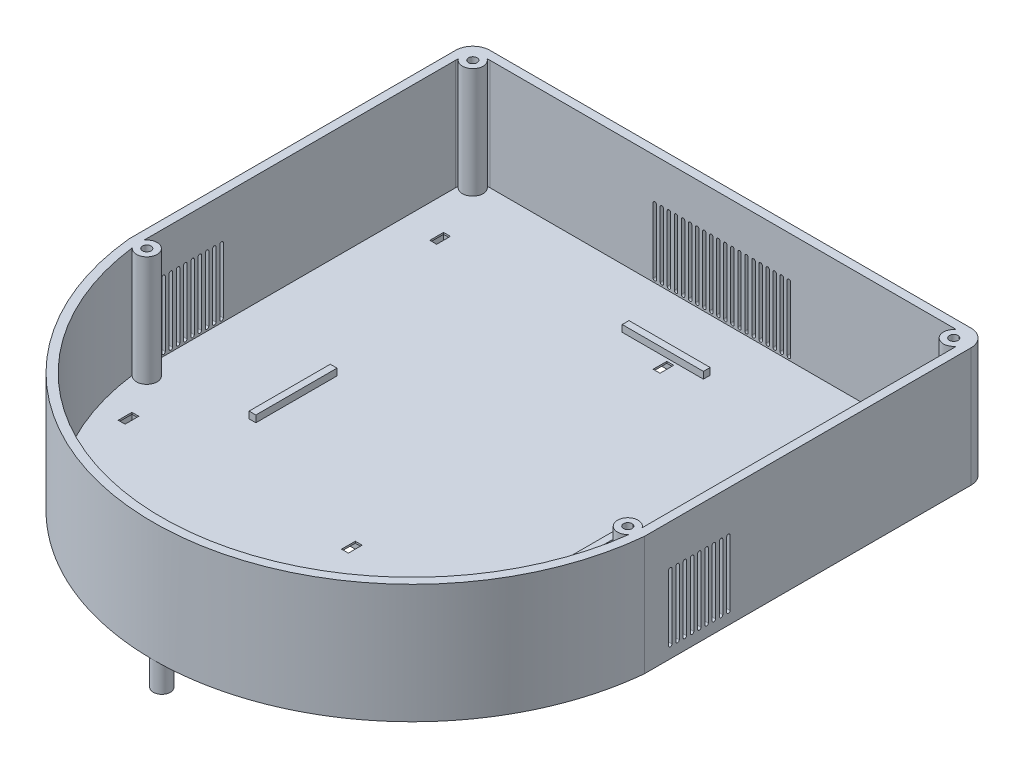
SolidWorks part; units mm, degrees
material "6063-O"
ref_plane "Front Plane" through (0, 0, 0) normal (0, 0, 1) x (1, 0, 0)
ref_plane "Top Plane" through (0, 0, 0) normal (0, 1, 0) x (1, 0, 0)
ref_plane "Right Plane" through (0, 0, 0) normal (1, 0, 0) x (0, 0, -1)
sketch "Sketch1" plane through (0, 0, 0) normal (0, 1, 0) x (1, 0, 0)
  line L1 (-190.5, -213.36) -> (190.5, -213.36)
  line L2 (-190.5, -213.36) -> (-190.5, 213.36)
  line L3 (-190.5, 213.36) -> (190.5, 213.36)
  line L4 (190.5, -213.36) -> (190.5, 213.36)
  line L5 (-190.5, -213.36) -> (190.5, 213.36) construction
  line L6 (-190.5, 213.36) -> (190.5, -213.36) construction
  arc A0 (190.5, -40.64) -> (-190.5, -40.64) centre (0, -21.9449) cw
  point P0 (0, 0)
  dimension "D1" = 381
  dimension "D2" = 426.72
  dimension "D3" = 254
extrude "Boss-Extrude1" add sketch "Sketch1" along normal blind 88 contours L4 L3 L2 L1 region at (0, 0, -17.9529)
shell "Shell1" thickness 6.35 removed face at (0, 88, -43.18)
fillet "Fillet2" radius 12.7 4 edges at (-190.5, 44, -213.36) (190.5, 44, -213.36) (184.15, 47.175, -207.01) (-184.15, 47.175, -207.01)
sketch "Sketch3" plane through (0, 6.35, 0) normal (0, 1, 0) x (1, 0, 0)
  line L0 (-177.8, 200.66) -> (-177.8, -40.3265) construction
  circle A2 centre (-177.8, 200.66) radius 7.62
  arc A5 (-177.8, 213.36) -> (-190.5, 200.66) centre (-177.8, 200.66) ccw construction
  circle A6 centre (-177.8, -40.3265) radius 7.62
  circle A8 centre (-177.8, 200.66) radius 3.175
  circle A9 centre (-177.8, -40.3265) radius 3.175
  dimension "D1" = 15.24
  dimension "D2" = 6.35
extrude "Boss-Extrude2" add sketch "Sketch3" along normal up to surface (81.65 mm away) up to face at (0, 88, -96.5501)
mirror "Mirror1" about plane through (0, 0, 0) normal (1, 0, 0) of "Boss-Extrude2"
sketch "Sketch4" plane through (0, 0, 0) normal (0, -1, 0) x (1, 0, 0)
  line L0 (-177.8, -213.36) -> (177.8, -213.36) construction
  line L1 (-161.29, -162.56) -> (161.29, -162.56)
  line L2 (-161.29, -162.56) -> (-161.29, -149.86)
  line L3 (-161.29, -149.86) -> (161.29, -149.86)
  line L4 (161.29, -162.56) -> (161.29, -149.86)
  line L5 (-161.29, 67.818) -> (161.29, 67.818)
  line L6 (-161.29, 67.818) -> (-161.29, 80.518)
  line L7 (-161.29, 80.518) -> (161.29, 80.518)
  line L8 (161.29, 67.818) -> (161.29, 80.518)
  point P8 (0, 80.518)
  dimension "D1" = 322.58
  dimension "D2" = 12.7
  dimension "D3" = 217.678
  dimension "D4" = 50.8
extrude "Cut-Extrude2" cut sketch "Sketch4" against normal blind 5.08
sketch "Sketch5" plane through (0, 5.08, 0) normal (0, -1, 0) x (1, 0, 0)
  line L1 (-160.02, 79.248) -> (-154.94, 79.248)
  line L2 (-160.02, 79.248) -> (-160.02, 69.088)
  line L3 (-160.02, 69.088) -> (-154.94, 69.088)
  line L4 (-154.94, 79.248) -> (-154.94, 69.088)
  line L5 (5.08, 79.248) -> (10.16, 79.248)
  line L6 (5.08, 79.248) -> (5.08, 69.088)
  line L7 (5.08, 69.088) -> (10.16, 69.088)
  line L8 (10.16, 79.248) -> (10.16, 69.088)
  line L9 (-161.29, 80.518) -> (-161.29, 67.818) construction
  line L10 (-161.29, 80.518) -> (-161.29, 67.818) construction
  line L11 (-161.29, -149.86) -> (-161.29, -162.56) construction
  line L12 (-160.02, -151.13) -> (-154.94, -151.13)
  line L13 (-160.02, -151.13) -> (-160.02, -161.29)
  line L14 (-160.02, -161.29) -> (-154.94, -161.29)
  line L15 (-154.94, -151.13) -> (-154.94, -161.29)
  line L16 (5.08, -151.13) -> (10.16, -151.13)
  line L17 (5.08, -151.13) -> (5.08, -161.29)
  line L18 (5.08, -161.29) -> (10.16, -161.29)
  line L19 (10.16, -151.13) -> (10.16, -161.29)
  point P12 (-161.29, 74.168)
  point P13 (-160.02, 74.168)
  point P14 (5.08, 74.168)
  point P25 (-161.29, -156.21)
  point P26 (-160.02, -156.21)
  point P27 (5.08, -156.21)
  dimension "D1" = 10.16
  dimension "D2" = 5.08
  dimension "D3" = 1.27
  dimension "D4" = 160.02
extrude "Cut-Extrude3" cut sketch "Sketch5" against normal through all
sketch "Sketch8" plane through (0, 0, -213.36) normal (0, 0, -1) x (-1, 0, 0)
  line L1 (177.8, 0) -> (-177.8, 0) construction
  line L2 (-50.8, 58.42) -> (50.8, 58.42)
  line L3 (-50.8, 58.42) -> (-50.8, 7.62)
  line L4 (-50.8, 7.62) -> (50.8, 7.62)
  line L5 (50.8, 58.42) -> (50.8, 7.62)
  line L6 (-50.8, 58.42) -> (50.8, 7.62) construction
  line L7 (-50.8, 7.62) -> (50.8, 58.42) construction
  line L8 (-49.53, 57.15) -> (-49.53, 8.89) construction
  line L9 (-48.26, 57.15) -> (-48.26, 8.89)
  line L10 (-50.8, 57.15) -> (-50.8, 8.89)
  line L11 (-45.5863, 57.15) -> (-45.5863, 8.89)
  line L12 (-43.0463, 57.15) -> (-43.0463, 8.89)
  line L13 (-44.3163, 57.15) -> (-44.3163, 8.89) construction
  line L14 (-40.3726, 57.15) -> (-40.3726, 8.89)
  line L15 (-37.8326, 57.15) -> (-37.8326, 8.89)
  line L16 (-39.1026, 57.15) -> (-39.1026, 8.89) construction
  line L17 (-35.1589, 57.15) -> (-35.1589, 8.89)
  line L18 (-32.6189, 57.15) -> (-32.6189, 8.89)
  line L19 (-33.8889, 57.15) -> (-33.8889, 8.89) construction
  line L20 (-29.9453, 57.15) -> (-29.9453, 8.89)
  line L21 (-27.4053, 57.15) -> (-27.4053, 8.89)
  line L22 (-28.6753, 57.15) -> (-28.6753, 8.89) construction
  line L23 (-24.7316, 57.15) -> (-24.7316, 8.89)
  line L24 (-22.1916, 57.15) -> (-22.1916, 8.89)
  line L25 (-23.4616, 57.15) -> (-23.4616, 8.89) construction
  line L26 (-19.5179, 57.15) -> (-19.5179, 8.89)
  line L27 (-16.9779, 57.15) -> (-16.9779, 8.89)
  line L28 (-18.2479, 57.15) -> (-18.2479, 8.89) construction
  line L29 (-14.3042, 57.15) -> (-14.3042, 8.89)
  line L30 (-11.7642, 57.15) -> (-11.7642, 8.89)
  line L31 (-13.0342, 57.15) -> (-13.0342, 8.89) construction
  line L32 (-9.0905, 57.15) -> (-9.0905, 8.89)
  line L33 (-6.5505, 57.15) -> (-6.5505, 8.89)
  line L34 (-7.8205, 57.15) -> (-7.8205, 8.89) construction
  line L35 (-3.8768, 57.15) -> (-3.8768, 8.89)
  line L36 (-1.3368, 57.15) -> (-1.3368, 8.89)
  line L37 (-2.6068, 57.15) -> (-2.6068, 8.89) construction
  line L38 (1.3368, 57.15) -> (1.3368, 8.89)
  line L39 (3.8768, 57.15) -> (3.8768, 8.89)
  line L40 (2.6068, 57.15) -> (2.6068, 8.89) construction
  line L41 (6.5505, 57.15) -> (6.5505, 8.89)
  line L42 (9.0905, 57.15) -> (9.0905, 8.89)
  line L43 (7.8205, 57.15) -> (7.8205, 8.89) construction
  line L44 (11.7642, 57.15) -> (11.7642, 8.89)
  line L45 (14.3042, 57.15) -> (14.3042, 8.89)
  line L46 (13.0342, 57.15) -> (13.0342, 8.89) construction
  line L47 (16.9779, 57.15) -> (16.9779, 8.89)
  line L48 (19.5179, 57.15) -> (19.5179, 8.89)
  line L49 (18.2479, 57.15) -> (18.2479, 8.89) construction
  line L50 (22.1916, 57.15) -> (22.1916, 8.89)
  line L51 (24.7316, 57.15) -> (24.7316, 8.89)
  line L52 (23.4616, 57.15) -> (23.4616, 8.89) construction
  line L53 (27.4053, 57.15) -> (27.4053, 8.89)
  line L54 (29.9453, 57.15) -> (29.9453, 8.89)
  line L55 (28.6753, 57.15) -> (28.6753, 8.89) construction
  line L56 (32.6189, 57.15) -> (32.6189, 8.89)
  line L57 (35.1589, 57.15) -> (35.1589, 8.89)
  line L58 (33.8889, 57.15) -> (33.8889, 8.89) construction
  line L59 (37.8326, 57.15) -> (37.8326, 8.89)
  line L60 (40.3726, 57.15) -> (40.3726, 8.89)
  line L61 (39.1026, 57.15) -> (39.1026, 8.89) construction
  line L62 (43.0463, 57.15) -> (43.0463, 8.89)
  line L63 (45.5863, 57.15) -> (45.5863, 8.89)
  line L64 (44.3163, 57.15) -> (44.3163, 8.89) construction
  line L65 (48.26, 57.15) -> (48.26, 8.89)
  line L66 (50.8, 57.15) -> (50.8, 8.89)
  line L67 (49.53, 57.15) -> (49.53, 8.89) construction
  arc A12 (-48.26, 57.15) -> (-50.8, 57.15) centre (-49.53, 57.15) ccw
  arc A13 (-50.8, 8.89) -> (-48.26, 8.89) centre (-49.53, 8.89) ccw
  arc A14 (-43.0463, 57.15) -> (-45.5863, 57.15) centre (-44.3163, 57.15) ccw
  arc A15 (-45.5863, 8.89) -> (-43.0463, 8.89) centre (-44.3163, 8.89) ccw
  arc A16 (-37.8326, 57.15) -> (-40.3726, 57.15) centre (-39.1026, 57.15) ccw
  arc A17 (-40.3726, 8.89) -> (-37.8326, 8.89) centre (-39.1026, 8.89) ccw
  arc A18 (-32.6189, 57.15) -> (-35.1589, 57.15) centre (-33.8889, 57.15) ccw
  arc A19 (-35.1589, 8.89) -> (-32.6189, 8.89) centre (-33.8889, 8.89) ccw
  arc A20 (-27.4053, 57.15) -> (-29.9453, 57.15) centre (-28.6753, 57.15) ccw
  arc A21 (-29.9453, 8.89) -> (-27.4053, 8.89) centre (-28.6753, 8.89) ccw
  arc A22 (-22.1916, 57.15) -> (-24.7316, 57.15) centre (-23.4616, 57.15) ccw
  arc A23 (-24.7316, 8.89) -> (-22.1916, 8.89) centre (-23.4616, 8.89) ccw
  arc A24 (-16.9779, 57.15) -> (-19.5179, 57.15) centre (-18.2479, 57.15) ccw
  arc A25 (-19.5179, 8.89) -> (-16.9779, 8.89) centre (-18.2479, 8.89) ccw
  arc A26 (-11.7642, 57.15) -> (-14.3042, 57.15) centre (-13.0342, 57.15) ccw
  arc A27 (-14.3042, 8.89) -> (-11.7642, 8.89) centre (-13.0342, 8.89) ccw
  arc A28 (-6.5505, 57.15) -> (-9.0905, 57.15) centre (-7.8205, 57.15) ccw
  arc A29 (-9.0905, 8.89) -> (-6.5505, 8.89) centre (-7.8205, 8.89) ccw
  arc A30 (-1.3368, 57.15) -> (-3.8768, 57.15) centre (-2.6068, 57.15) ccw
  arc A31 (-3.8768, 8.89) -> (-1.3368, 8.89) centre (-2.6068, 8.89) ccw
  arc A32 (3.8768, 57.15) -> (1.3368, 57.15) centre (2.6068, 57.15) ccw
  arc A33 (1.3368, 8.89) -> (3.8768, 8.89) centre (2.6068, 8.89) ccw
  arc A34 (9.0905, 57.15) -> (6.5505, 57.15) centre (7.8205, 57.15) ccw
  arc A35 (6.5505, 8.89) -> (9.0905, 8.89) centre (7.8205, 8.89) ccw
  arc A36 (14.3042, 57.15) -> (11.7642, 57.15) centre (13.0342, 57.15) ccw
  arc A37 (11.7642, 8.89) -> (14.3042, 8.89) centre (13.0342, 8.89) ccw
  arc A38 (19.5179, 57.15) -> (16.9779, 57.15) centre (18.2479, 57.15) ccw
  arc A39 (16.9779, 8.89) -> (19.5179, 8.89) centre (18.2479, 8.89) ccw
  arc A40 (24.7316, 57.15) -> (22.1916, 57.15) centre (23.4616, 57.15) ccw
  arc A41 (22.1916, 8.89) -> (24.7316, 8.89) centre (23.4616, 8.89) ccw
  arc A42 (29.9453, 57.15) -> (27.4053, 57.15) centre (28.6753, 57.15) ccw
  arc A43 (27.4053, 8.89) -> (29.9453, 8.89) centre (28.6753, 8.89) ccw
  arc A44 (35.1589, 57.15) -> (32.6189, 57.15) centre (33.8889, 57.15) ccw
  arc A45 (32.6189, 8.89) -> (35.1589, 8.89) centre (33.8889, 8.89) ccw
  arc A46 (40.3726, 57.15) -> (37.8326, 57.15) centre (39.1026, 57.15) ccw
  arc A47 (37.8326, 8.89) -> (40.3726, 8.89) centre (39.1026, 8.89) ccw
  arc A48 (45.5863, 57.15) -> (43.0463, 57.15) centre (44.3163, 57.15) ccw
  arc A49 (43.0463, 8.89) -> (45.5863, 8.89) centre (44.3163, 8.89) ccw
  arc A50 (50.8, 57.15) -> (48.26, 57.15) centre (49.53, 57.15) ccw
  arc A51 (48.26, 8.89) -> (50.8, 8.89) centre (49.53, 8.89) ccw
  point P0 (0, 33.02)
  point P12 (-49.53, 33.02)
  point P21 (-44.3163, 33.02)
  point P28 (-39.1026, 33.02)
  point P36 (-33.8889, 33.02)
  point P43 (-28.6753, 33.02)
  point P50 (-23.4616, 33.02)
  point P57 (-18.2479, 33.02)
  point P64 (-13.0342, 33.02)
  point P71 (-7.8205, 33.02)
  point P78 (-2.6068, 33.02)
  point P85 (2.6068, 33.02)
  point P92 (7.8205, 33.02)
  point P99 (13.0342, 33.02)
  point P106 (18.2479, 33.02)
  point P113 (23.4616, 33.02)
  point P120 (28.6753, 33.02)
  point P127 (33.8889, 33.02)
  point P134 (39.1026, 33.02)
  point P141 (44.3163, 33.02)
  point P148 (49.53, 33.02)
  dimension "D1" = 101.6
  dimension "D2" = 50.8
  dimension "D3" = 7.62
  dimension "D4" = 2.54
  dimension "D5" = 20
extrude "Cut-Extrude4" cut sketch "Sketch8" against normal up to surface (6.35 mm away) contours L10 A13 L9 A12 | L12 A15 L11 A14 | L15 A17 L14 A16 | L18 A19 L17 A18 | L21 A21 L20 A20 | L24 A23 L23 A22 | L27 A25 L26 A24 | L30 A27 L29 A26 | L33 A29 L32 A28 | L36 A31 L35 A30 | L39 A33 L38 A32 | L42 A35 L41 A34 | L45 A37 L44 A36 | L48 A39 L47 A38 | L51 A41 L50 A40 | L54 A43 L53 A42 | L57 A45 L56 A44 | L60 A47 L59 A46 | L63 A49 L62 A48 | L66 A51 L65 A50 up to face at (0, 47.175, -207.01)
sketch "Sketch10" plane through (190.5, 0, 0) normal (1, 0, 0) x (0, 0, -1)
  line L0 (-22.86, 58.42) -> (27.94, 58.42)
  line L1 (-22.86, 58.42) -> (-22.86, 7.62)
  line L2 (-22.86, 7.62) -> (27.94, 7.62)
  line L3 (27.94, 58.42) -> (27.94, 7.62)
  line L4 (-22.86, 58.42) -> (27.94, 7.62) construction
  line L5 (-22.86, 7.62) -> (27.94, 58.42) construction
  line L6 (-40.64, 88) -> (-40.64, 0) construction
  line L11 (-40.64, 0) -> (200.66, 0) construction
  line L14 (-21.59, 57.15) -> (-21.59, 8.89) construction
  line L17 (-20.32, 57.15) -> (-20.32, 8.89)
  line L20 (-22.86, 57.15) -> (-22.86, 8.89)
  line L23 (-17.4978, 57.15) -> (-17.4978, 8.89)
  line L26 (-14.9578, 57.15) -> (-14.9578, 8.89)
  line L29 (-16.2278, 57.15) -> (-16.2278, 8.89) construction
  line L32 (-12.1356, 57.15) -> (-12.1356, 8.89)
  line L35 (-9.5956, 57.15) -> (-9.5956, 8.89)
  line L38 (-10.8656, 57.15) -> (-10.8656, 8.89) construction
  line L41 (-6.7733, 57.15) -> (-6.7733, 8.89)
  line L44 (-4.2333, 57.15) -> (-4.2333, 8.89)
  line L47 (-5.5033, 57.15) -> (-5.5033, 8.89) construction
  line L50 (-1.4111, 57.15) -> (-1.4111, 8.89)
  line L53 (1.1289, 57.15) -> (1.1289, 8.89)
  line L56 (-0.1411, 57.15) -> (-0.1411, 8.89) construction
  line L59 (3.9511, 57.15) -> (3.9511, 8.89)
  line L62 (6.4911, 57.15) -> (6.4911, 8.89)
  line L65 (5.2211, 57.15) -> (5.2211, 8.89) construction
  line L66 (9.3133, 57.15) -> (9.3133, 8.89)
  line L67 (11.8533, 57.15) -> (11.8533, 8.89)
  line L68 (10.5833, 57.15) -> (10.5833, 8.89) construction
  line L69 (14.6756, 57.15) -> (14.6756, 8.89)
  line L70 (17.2156, 57.15) -> (17.2156, 8.89)
  line L71 (15.9456, 57.15) -> (15.9456, 8.89) construction
  line L72 (20.0378, 57.15) -> (20.0378, 8.89)
  line L73 (22.5778, 57.15) -> (22.5778, 8.89)
  line L74 (21.3078, 57.15) -> (21.3078, 8.89) construction
  line L75 (25.4, 57.15) -> (25.4, 8.89)
  line L76 (27.94, 57.15) -> (27.94, 8.89)
  line L77 (26.67, 57.15) -> (26.67, 8.89) construction
  arc A40 (-20.32, 57.15) -> (-22.86, 57.15) centre (-21.59, 57.15) ccw
  arc A41 (-22.86, 8.89) -> (-20.32, 8.89) centre (-21.59, 8.89) ccw
  arc A42 (-14.9578, 57.15) -> (-17.4978, 57.15) centre (-16.2278, 57.15) ccw
  arc A43 (-17.4978, 8.89) -> (-14.9578, 8.89) centre (-16.2278, 8.89) ccw
  arc A44 (-9.5956, 57.15) -> (-12.1356, 57.15) centre (-10.8656, 57.15) ccw
  arc A45 (-12.1356, 8.89) -> (-9.5956, 8.89) centre (-10.8656, 8.89) ccw
  arc A46 (-4.2333, 57.15) -> (-6.7733, 57.15) centre (-5.5033, 57.15) ccw
  arc A47 (-6.7733, 8.89) -> (-4.2333, 8.89) centre (-5.5033, 8.89) ccw
  arc A48 (1.1289, 57.15) -> (-1.4111, 57.15) centre (-0.1411, 57.15) ccw
  arc A49 (-1.4111, 8.89) -> (1.1289, 8.89) centre (-0.1411, 8.89) ccw
  arc A50 (6.4911, 57.15) -> (3.9511, 57.15) centre (5.2211, 57.15) ccw
  arc A51 (3.9511, 8.89) -> (6.4911, 8.89) centre (5.2211, 8.89) ccw
  arc A52 (11.8533, 57.15) -> (9.3133, 57.15) centre (10.5833, 57.15) ccw
  arc A53 (9.3133, 8.89) -> (11.8533, 8.89) centre (10.5833, 8.89) ccw
  arc A54 (17.2156, 57.15) -> (14.6756, 57.15) centre (15.9456, 57.15) ccw
  arc A55 (14.6756, 8.89) -> (17.2156, 8.89) centre (15.9456, 8.89) ccw
  arc A56 (22.5778, 57.15) -> (20.0378, 57.15) centre (21.3078, 57.15) ccw
  arc A57 (20.0378, 8.89) -> (22.5778, 8.89) centre (21.3078, 8.89) ccw
  arc A58 (27.94, 57.15) -> (25.4, 57.15) centre (26.67, 57.15) ccw
  arc A59 (25.4, 8.89) -> (27.94, 8.89) centre (26.67, 8.89) ccw
  point P0 (2.54, 33.02)
  point P9 (-21.59, 33.02)
  point P20 (-16.2278, 33.02)
  point P27 (-10.8656, 33.02)
  point P34 (-5.5033, 33.02)
  point P41 (-0.1411, 33.02)
  point P48 (5.2211, 33.02)
  point P55 (10.5833, 33.02)
  point P62 (15.9456, 33.02)
  point P69 (21.3078, 33.02)
  point P76 (26.67, 33.02)
  dimension "D1" = 7.62
  dimension "D2" = 50.8
  dimension "D3" = 50.8
  dimension "D4" = 17.78
  dimension "D5" = 2.54
  dimension "D6" = 10
extrude "Cut-Extrude5" cut sketch "Sketch10" against normal up to surface (6.35 mm away) contours L1 A41 L17 A40 | L23 A43 L26 A42 | L41 A47 L44 A46 | L59 A51 L62 A50 | L66 A53 L67 A52 | L69 A55 L70 A54 | L72 A57 L73 A56 | L32 A45 L35 A44 | L53 A49 L50 A48 region at (190.5, 33.02, 21.59) region at (190.5, 33.02, 16.2278) region at (190.5, 33.02, 5.5033) region at (190.5, 33.02, -5.2211) region at (190.5, 33.02, -10.5833) region at (190.5, 33.02, -15.9456) region at (190.5, 33.02, -21.3078) up to face at (184.15, 47.175, -79.0978)
mirror "Mirror2" about plane through (0, 0, 0) normal (1, 0, 0) of "Cut-Extrude5"
sketch "Sketch11" plane through (0, 0, 0) normal (0, -1, 0) x (1, 0, 0)
  circle A0 centre (0, 207.01) radius 6.35
  arc A1 (190.5, 40.64) -> (-190.5, 40.64) centre (0, 21.9449) ccw construction
  circle A2 centre (0, 207.01) radius 3.81
  dimension "D1" = 12.7
  dimension "D2" = 7.62
extrude "Boss-Extrude4" add sketch "Sketch11" along normal blind 20.78
sketch "Sketch13" plane through (0, 6.35, 0) normal (0, 1, 0) x (1, 0, 0)
  line L0 (-177.8, 213.36) -> (177.8, 213.36) construction
  line L1 (-107.5, 163.36) -> (107.5, 163.36)
  line L2 (-107.5, 163.36) -> (-107.5, -165.64)
  line L3 (-107.5, -165.64) -> (107.5, -165.64)
  line L4 (107.5, 163.36) -> (107.5, -165.64)
  line L5 (-107.5, 30) -> (-112.5, 30)
  line L6 (-107.5, 30) -> (-107.5, -30)
  line L7 (-107.5, -30) -> (-112.5, -30)
  line L8 (-112.5, 30) -> (-112.5, -30)
  line L9 (99.15, 30) -> (104.15, 30)
  line L10 (99.15, 30) -> (99.15, -30)
  line L11 (99.15, -30) -> (104.15, -30)
  line L12 (104.15, 30) -> (104.15, -30)
  line L13 (-30, -165.64) -> (30, -165.64)
  line L14 (-30, -165.64) -> (-30, -170.64)
  line L15 (-30, -170.64) -> (30, -170.64)
  line L16 (30, -165.64) -> (30, -170.64)
  line L17 (-30, 163.36) -> (30, 163.36)
  line L18 (-30, 163.36) -> (-30, 168.36)
  line L19 (-30, 168.36) -> (30, 168.36)
  line L20 (30, 163.36) -> (30, 168.36)
  line L21 (-184.15, -36.1144) -> (-184.15, 194.31) construction
  line L22 (184.15, -36.1144) -> (184.15, 194.31) construction
  point P5 (0, -170.64)
  point P15 (-112.5, 0)
  point P17 (104.15, 0)
  point P27 (0, 168.36)
  line M13 (5.08, 151.13) -> (5.08, 161.29)
  line M14 (5.08, 161.29) -> (10.16, 161.29)
  line M15 (10.16, 161.29) -> (10.16, 151.13)
  dimension "D1" = 215
  dimension "D2" = 329
  dimension "D3" = 60
  dimension "D4" = 5
  dimension "D5" = 60
  dimension "D6" = 5
  dimension "D7" = 5
  dimension "D8" = 60
  dimension "D9" = 60
  dimension "D10" = 5
  dimension "D11" = 50
  dimension "D12" = 76.65
  dimension "D13" = 80
extrude "Boss-Extrude5" add sketch "Sketch13" along normal blind 5 contours L1 L20 L19 L18 M13 M14 M15 | L5 L8 L7 L2 | L16 L3 L14 L15 | L12 L11 L10 L9 region at (0, 6.35, -165.86) region at (-110, 6.35, 0) region at (0, 6.35, 168.14)
sketch "Sketch14" plane through (0, 0, 0) normal (0, -1, 0) x (1, 0, 0)
  line L0 (0, -213.36) -> (0, 213.36) construction
  line L1 (-177.8, -213.36) -> (177.8, -213.36) construction
  circle A0 centre (0, 152.1691) radius 40.8303
